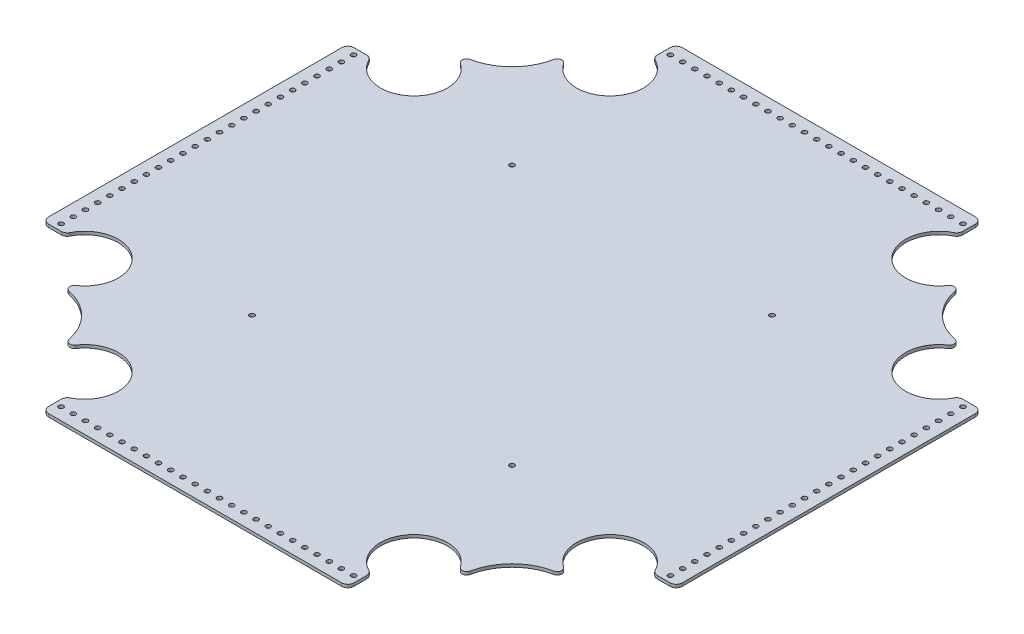
SolidWorks part; units mm, degrees
material "PC High Viscosity"
ref_plane "Front Plane" through (0, 0, 0) normal (0, 0, 1) x (1, 0, 0)
ref_plane "Top Plane" through (0, 0, 0) normal (0, 1, 0) x (1, 0, 0)
ref_plane "Right Plane" through (0, 0, 0) normal (1, 0, 0) x (0, 0, -1)
sketch "Sketch1" plane through (0, 0, 0) normal (0, 1, 0) x (1, 0, 0)
  line L1 (330.2, 330.2) -> (-330.2, 330.2)
  line L2 (330.2, 330.2) -> (330.2, -330.2)
  line L3 (330.2, -330.2) -> (-330.2, -330.2)
  line L4 (-330.2, 330.2) -> (-330.2, -330.2)
  line L5 (330.2, 330.2) -> (-330.2, -330.2) construction
  line L6 (330.2, -330.2) -> (-330.2, 330.2) construction
  point P0 (0, 0)
  dimension "D1" = 660.4
extrude "Boss-Extrude1" add sketch "Sketch1" along normal mid plane 3.175
sketch "Sketch2" plane through (0, 1.5875, 0) normal (0, 1, 0) x (1, 0, 0)
  line L0 (-330.2, -330.2) -> (330.2, -330.2) construction
  line L1 (-330.2, 330.2) -> (-330.2, -330.2) construction
  circle A0 centre (-317.5, -317.5) radius 2.4892
  dimension "D1" = 4.9784
  dimension "D2" = 12.7
  dimension "D3" = 12.7
extrude "Cut-Extrude1" cut sketch "Sketch2" against normal through all
pattern_linear "LPattern1" count 51 spacing 12.7 along (0, 0, -1) count 51 spacing 12.7 along (1, 0, 0) of "Cut-Extrude1" pattern seed only yes
pattern_linear "LPattern2" count 51 spacing 12.7 along (0, 0, -1) of face at (317.5, -1.5875, 319.9892)
pattern_linear "LPattern3" count 50 spacing 12.7 along (1, 0, 0) of face at (-317.5, -1.5875, -315.0108)
sketch "Sketch4" plane through (0, -1.5875, 0) normal (0, -1, 0) x (-1, 0, 0)
  line L0 (-330.2, 159.131) -> (-306.3652, 159.131)
  line L1 (-330.2, -330.2) -> (-330.2, 330.2) construction
  line L2 (-320.675, 160.7185) -> (-314.325, 160.7185) construction
  line L3 (-159.131, 330.2) -> (-159.131, 306.3652)
  line L4 (-330.2, 330.2) -> (330.2, 330.2) construction
  line L5 (-159.131, 330.2) -> (-330.2, 330.2)
  line L6 (-330.2, 330.2) -> (-330.2, 159.131)
  circle A0 centre (-263.525, 263.525) radius 55.5625
  arc A1 (-232.9401, 309.912) -> (-319.0875, 263.525) centre (-263.525, 263.525) ccw construction
  circle A2 centre (-171.45, 273.685) radius 34.925
  circle A3 centre (-273.685, 171.45) radius 34.925
  arc A4 (-140.716, 273.685) -> (-171.45, 304.419) centre (-171.45, 273.685) ccw construction
  arc A5 (-304.8, 171.45) -> (-251.6834, 149.4484) centre (-273.685, 171.45) ccw construction
  arc A6 (-254.2153, 200.4446) -> (-252.5049, 209.0663) centre (-251.5604, 204.3984) cw
  arc A7 (-209.0663, 252.5049) -> (-200.4446, 254.2153) centre (-204.3984, 251.5604) cw
  dimension "D1" = 69.85
  dimension "D2" = 1.5875
  dimension "D3" = 4.7625
extrude "Cut-Extrude2" cut sketch "Sketch4" against normal through all contours A0 A7 A2 L3 L5 L6 L0 A3 A6 | A0 | A3 | A2 region at (327.7807, -1.5875, -244.6655) region at (273.685, -1.5875, -171.45) region at (263.525, -1.5875, -263.525) region at (171.45, -1.5875, -273.685)
mirror "Mirror2" about plane through (0, 0, 0) normal (1, 0, 0) of "Cut-Extrude2"
mirror "Mirror3" about plane through (0, 0, 0) normal (0, 0, 1) of "Cut-Extrude2", "Mirror2"
fillet "Fillet1" radius 6.35 16 edges at (-330.2, 0, -159.131) (-306.3652, 0, -159.131) (-159.131, 0, -306.3652) (-159.131, 0, -330.2) (159.131, 0, -330.2) (159.131, 0, -306.3652) (306.3652, 0, -159.131) (330.2, 0, -159.131) (330.2, 0, 159.131) (306.3652, 0, 159.131) (159.131, 0, 306.3652) (159.131, 0, 330.2) (-159.131, 0, 330.2) (-159.131, 0, 306.3652) (-330.2, 0, 159.131) (-306.3652, 0, 159.131)
sketch "Sketch5" plane through (0, -1.5875, 0) normal (0, -1, 0) x (1, 0, 0)
  circle A0 centre (135.4667, 135.4667) radius 2.4892 construction
  circle A1 centre (135.4667, -135.4667) radius 2.4892 construction
  circle A2 centre (-135.4667, -135.4667) radius 2.4892 construction
  circle A3 centre (-135.4667, 135.4667) radius 2.4892 construction
  circle A4 centre (135.4667, 135.4667) radius 2.4892
  circle A5 centre (135.4667, -135.4667) radius 2.4892
  circle A6 centre (-135.4667, -135.4667) radius 2.4892
  circle A7 centre (-135.4667, 135.4667) radius 2.4892
extrude "Cut-Extrude3" cut sketch "Sketch5" against normal through all
